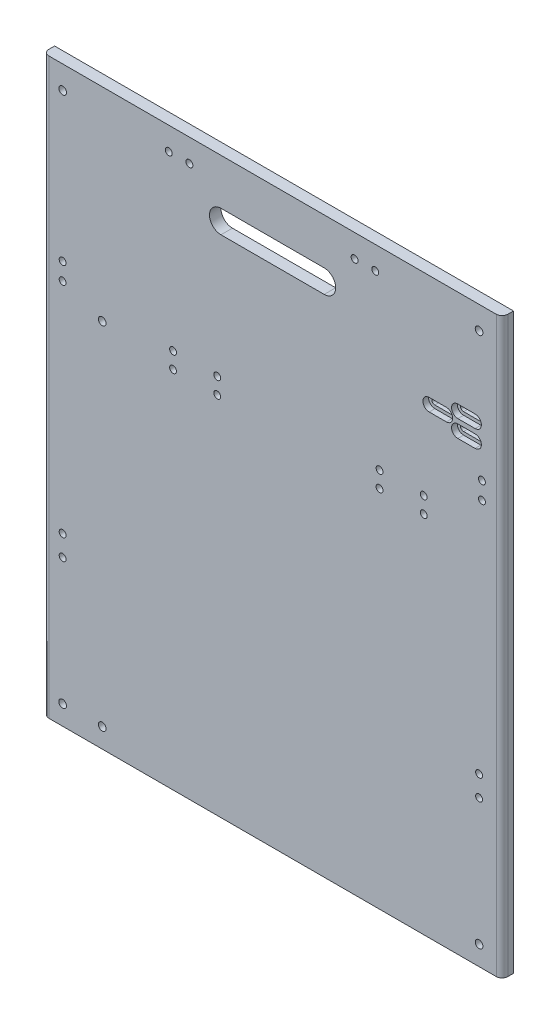
SolidWorks part; units mm, degrees
note: The reader was unsure of these and kept them because the rebuilt part matched: shared geometry of "Sketch18<4>".
ref_plane "Front Plane" through (0, 0, 0) normal (0, 0, 1) x (1, 0, 0)
ref_plane "Top Plane" through (0, 0, 0) normal (0, 1, 0) x (1, 0, 0)
ref_plane "Right Plane" through (0, 0, 0) normal (1, 0, 0) x (0, 0, -1)
sketch "Sketch1" plane through (0, 0, 0) normal (0, 0, 1) x (1, 0, 0)
  line L1 (0, 0) -> (400, 0)
  line L2 (0, 0) -> (0, 500)
  line L3 (0, 500) -> (400, 500)
  line L4 (400, 0) -> (400, 500)
  dimension "D1" = 400
  dimension "D2" = 500
extrude "Boss-Extrude1" add sketch "Sketch1" along normal blind 10 contours L2 L1 L4 L3
sketch "Sketch15" plane through (0, 0, 10) normal (0, 0, 1) x (1, 0, 0)
  line L0 (155, 450) -> (245, 450) construction
  line L1 (155, 460) -> (245, 460)
  line L2 (155, 440) -> (245, 440)
  line L3 (200, 450) -> (200, 500) construction
  line L4 (0, 500) -> (400, 500) construction
  arc A0 (155, 460) -> (155, 440) centre (155, 450) ccw
  arc A1 (245, 440) -> (245, 460) centre (245, 450) ccw
  point P2 (200, 450)
  dimension "D1" = 10
  dimension "D2" = 90
  dimension "D3" = 50
extrude "Cut-Extrude12" cut sketch "Sketch15" against normal blind 20
fillet "Fillet2" radius 5 2 edges at (0, 250, 10) (400, 250, 10)
sketch "Sketch18" plane through (0, 0, 10) normal (0, 0, 1) x (1, 0, 0)
  line L0 (351.5, 402.5) -> (336.5, 402.5) construction
  line L1 (351.5, 399.75) -> (336.5, 399.75)
  line L2 (351.5, 405.25) -> (336.5, 405.25)
  line L3 (376.5, 410) -> (361.5, 410) construction
  line L4 (376.5, 407.25) -> (361.5, 407.25)
  line L5 (376.5, 412.75) -> (361.5, 412.75)
  line L6 (376.5, 395) -> (361.5, 395) construction
  line L7 (376.5, 392.25) -> (361.5, 392.25)
  line L8 (376.5, 397.75) -> (361.5, 397.75)
  line L9 (351.5, 402.5) -> (336.5, 402.5) construction
  line L10 (351.5, 397) -> (336.5, 397)
  line L11 (351.5, 408) -> (336.5, 408)
  line L12 (376.5, 410) -> (361.5, 410) construction
  line L13 (376.5, 404.5) -> (361.5, 404.5)
  line L14 (376.5, 415.5) -> (361.5, 415.5)
  line L15 (376.5, 395) -> (361.5, 395) construction
  line L16 (376.5, 389.5) -> (361.5, 389.5)
  line L17 (376.5, 400.5) -> (361.5, 400.5)
  arc A6 (351.5, 399.75) -> (351.5, 405.25) centre (351.5, 402.5) ccw
  arc A7 (336.5, 405.25) -> (336.5, 399.75) centre (336.5, 402.5) ccw
  arc A8 (376.5, 407.25) -> (376.5, 412.75) centre (376.5, 410) ccw
  arc A9 (361.5, 412.75) -> (361.5, 407.25) centre (361.5, 410) ccw
  arc A10 (376.5, 392.25) -> (376.5, 397.75) centre (376.5, 395) ccw
  arc A11 (361.5, 397.75) -> (361.5, 392.25) centre (361.5, 395) ccw
  arc A13 (351.5, 397) -> (351.5, 408) centre (351.5, 402.5) ccw
  arc A14 (336.5, 408) -> (336.5, 397) centre (336.5, 402.5) ccw
  arc A15 (376.5, 404.5) -> (376.5, 415.5) centre (376.5, 410) ccw
  arc A16 (361.5, 415.5) -> (361.5, 404.5) centre (361.5, 410) ccw
  arc A17 (376.5, 389.5) -> (376.5, 400.5) centre (376.5, 395) ccw
  arc A18 (361.5, 400.5) -> (361.5, 389.5) centre (361.5, 395) ccw
  point P2 (344, 402.5)
  point P7 (369, 410)
  point P16 (369, 395)
  point P28 (344, 402.5)
  point P33 (369, 410)
  point P40 (369, 395)
  dimension "D1" = 15
  dimension "D2" = 11
extrude "Cut-Extrude16" cut sketch "Sketch18" against normal blind 32 contours L2 A7 L1 A6 | L5 A9 L4 A8 | L8 A11 L7 A10
ref_plane "Plane1" through (410, 0, 0) normal (1, 0, 0) x (0, 0, -1)
mirror "Mirror1" [suppressed] about plane through (410, 0, 0) normal (1, 0, 0)
extrude "Cut-Extrude17" cut sketch "Sketch19" against normal blind 124
sketch "Sketch19" plane through (0, 0, 0) normal (0, 0, -1) x (-1, 0, 0)
  circle A27 centre (-380, 145.5) radius 3
  circle A28 centre (-380, 127.5) radius 3
  circle A29 centre (-380, 17) radius 3.35
  circle A30 centre (-17, 17) radius 3.35
  circle A31 centre (-17, 145.5) radius 3
  circle A32 centre (-17, 127.5) radius 3
  circle A33 centre (-113.25, 317.5) radius 3
  circle A34 centre (-113.25, 331.5) radius 3
  circle A35 centre (-151.75, 317.5) radius 3
  circle A36 centre (-151.75, 331.5) radius 3
  circle A37 centre (-293.25, 317.5) radius 3
  circle A38 centre (-293.25, 331.5) radius 3
  circle A39 centre (-331.75, 317.5) radius 3
  circle A40 centre (-331.75, 331.5) radius 3
  circle A41 centre (-17, 336) radius 3
  circle A42 centre (-17, 351) radius 3
  circle A43 centre (-17, 480) radius 3.35
  circle A44 centre (-109.5, 480) radius 3
  circle A45 centre (-127.5, 480) radius 3
  circle A46 centre (-271.5, 480) radius 3
  circle A47 centre (-289.5, 480) radius 3
  circle A48 centre (-380, 480) radius 3.35
  circle A49 centre (-351.5, 402.5) radius 2.75
  circle A50 centre (-382.5, 353.25) radius 3
  circle A51 centre (-382.5, 368.25) radius 3
  circle A52 centre (-376.5, 410) radius 2.75
  circle A53 centre (-376.5, 395) radius 2.75
  circle A54 centre (-51.5, 323) radius 3.35
  circle A55 centre (-51.5, 17) radius 3.35
  point P0 (-51.5, 17)
  point P61 (-51.5, 323)
  point P62 (-347.5, 17)
extrude "Cut-Extrude18" cut sketch "Sketch18<4>" against normal blind 5
sketch "Sketch18<4>" plane through (0, 0, 10) normal (0, 0, 1) x (1, 0, 0) same geometry as "Sketch18"
